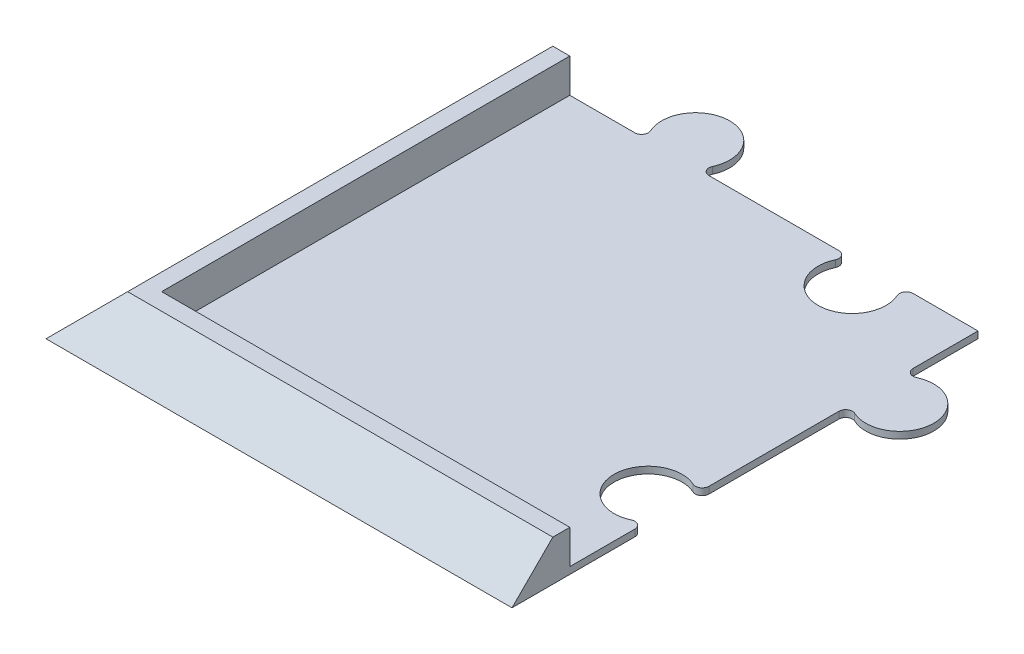
SolidWorks part; units mm, degrees
material "ABS"
ref_plane "Front Plane" through (0, 0, 0) normal (0, 0, 1) x (1, 0, 0)
ref_plane "Top Plane" through (0, 0, 0) normal (0, 1, 0) x (1, 0, 0)
ref_plane "Right Plane" through (0, 0, 0) normal (1, 0, 0) x (0, 0, -1)
sketch "Sketch1" plane through (0, 0, 0) normal (0, 0, 1) x (1, 0, 0)
  line L0 (0, 0) -> (0, 82.3894) construction
  line L1 (0, 0) -> (-173.99, 0)
  line L2 (-173.99, 0) -> (-158.75, 15.24)
  line L3 (-158.75, 15.24) -> (-152.4, 15.24)
  line L4 (-152.4, 15.24) -> (-152.4, 2.54)
  line L5 (-152.4, 2.54) -> (0, 2.54)
  line L6 (0, 2.54) -> (0, 0)
  dimension "D1" = 6.35
  dimension "D2" = 152.4
  dimension "D3" = 45
  dimension "D4" = 2.54
  dimension "D5" = 12.7
extrude "Boss-Extrude1" add sketch "Sketch1" along normal blind 152.4 contours L4 L5 L6 L1 L2 L3
sketch "Sketch2" plane through (0, 0, 0) normal (1, 0, 0) x (0, 0, -1)
  line L0 (-152.4, 2.54) -> (-152.4, 15.24)
  line L1 (-152.4, 15.24) -> (-158.75, 15.24)
  line L2 (-158.75, 15.24) -> (-173.99, 0)
  line L3 (-173.99, 0) -> (-152.4, 0)
  line L4 (-152.4, 0) -> (-152.4, 2.54)
  dimension "D1" = 45
  dimension "D2" = 6.35
extrude "Boss-Extrude2" add sketch "Sketch2" against normal through all
sketch "Sketch3" plane through (0, 0, 152.4) normal (0, 0, -1) x (-1, 0, 0)
  line L3 (158.75, 15.24) -> (173.99, 0)
  line L4 (173.99, 0) -> (173.99, 15.24)
  line L5 (173.99, 15.24) -> (158.75, 15.24)
  line L6 (158.75, 15.24) -> (173.99, 0)
  line L7 (173.99, 0) -> (173.99, 15.24)
  line L8 (173.99, 15.24) -> (158.75, 15.24)
  dimension "D1" = 0
extrude "Cut-Extrude1" cut sketch "Sketch3" against normal through all
sketch "Sketch4" plane through (0, 2.54, 0) normal (0, 1, 0) x (1, 0, 0)
  line L0 (-76.2, 0) -> (-76.2, -63.2185) construction
  line L2 (-152.4, 0) -> (0, 0) construction
  line L3 (-78.0415, -76.2) -> (75.2619, -76.2) construction
  line L4 (0, -152.4) -> (0, 0) construction
  line L5 (-123.3696, 0) -> (-105.2304, 0)
  line L6 (-47.1696, 0) -> (-29.0304, 0)
  line L7 (0, -29.0304) -> (0, -47.1696)
  line L8 (0, -105.2304) -> (0, -123.3696)
  arc A0 (-123.3696, 0) -> (-105.2304, 0) centre (-114.3, 8.89) cw
  arc A1 (-47.1696, 0) -> (-29.0304, 0) centre (-38.1, -8.89) ccw
  arc A2 (0, -29.0304) -> (0, -47.1696) centre (8.89, -38.1) cw
  arc A3 (0, -105.2304) -> (0, -123.3696) centre (-8.89, -114.3) ccw
  point P3 (-76.2, 0)
  point P15 (0, -76.2)
  line M3 (0, 0) -> (-152.4, 0)
  line M6 (0, -152.4) -> (0, 0)
  dimension "D2" = 12.7
  dimension "D6" = 12.7
  dimension "D9" = 12.7
  dimension "D10" = 12.7
  dimension "D1" = 38.1
  dimension "D3" = 8.89
  dimension "D4" = 38.1
  dimension "D5" = 8.89
  dimension "D7" = 8.89
  dimension "D8" = 38.1
  dimension "D11" = 38.1
  dimension "D12" = 8.89
extrude "Boss-Extrude3" add sketch "Sketch4" against normal through all contours A0 M3 | A2 M6 region at (-114.3, 2.54, -9.9735) region at (9.9735, 2.54, 38.1)
extrude "Cut-Extrude2" cut sketch "Sketch4<3>" against normal through all contours A1 M3 | A3 M6 region at (-9.9735, 2.54, 114.3) region at (-38.1, 2.54, 9.9735)
sketch "Sketch4<3>" plane through (0, 2.54, 0) normal (0, 1, 0) x (1, 0, 0) same geometry as "Sketch4"
fillet "Fillet1" radius 2.54 8 edges at (0, 1.27, 123.3696) (0, 1.27, 105.2304) (0, 1.27, 47.1696) (0, 1.27, 29.0304) (-29.0304, 1.27, 0) (-47.1696, 1.27, 0) (-105.2304, 1.27, 0) (-123.3696, 1.27, 0)
equation "\"D5@Sketch4\"=\"D3@Sketch4\""
equation "\"D7@Sketch4\"=\"D3@Sketch4\""
equation "\"D12@Sketch4\"=\"D3@Sketch4\""
